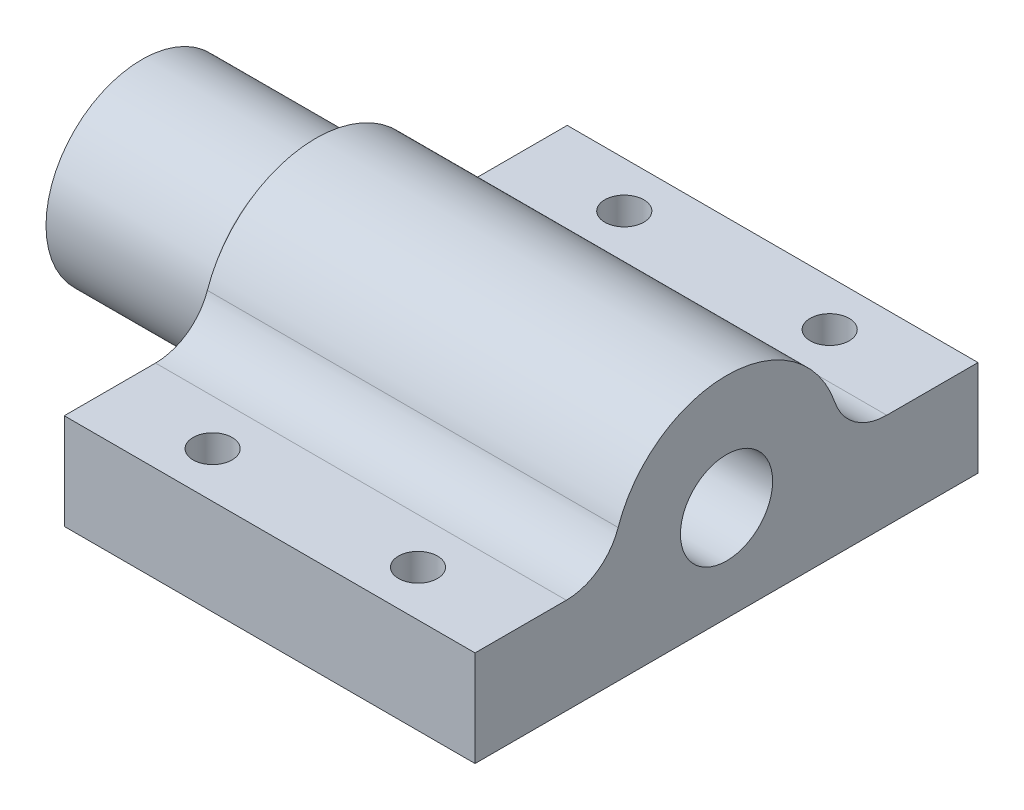
SolidWorks part; units mm, degrees
ref_plane "Front Plane" through (0, 0, 0) normal (0, 0, 1) x (1, 0, 0)
ref_plane "Top Plane" through (0, 0, 0) normal (0, 1, 0) x (1, 0, 0)
ref_plane "Right Plane" through (0, 0, 0) normal (1, 0, 0) x (0, 0, -1)
sketch "Sketch1" plane through (0, 0, 0) normal (1, 0, 0) x (0, 0, -1)
  line L0 (-11.7007, 0) -> (-18.3655, 0)
  line L1 (-18.3655, 0) -> (-18.3655, -7)
  line L2 (-18.3655, -7) -> (18.3655, -7)
  line L3 (0, 0) -> (0, -30.6301) construction
  line L4 (18.3655, 0) -> (18.3655, -7)
  line L5 (11.7007, 0) -> (18.3655, 0)
  circle A0 centre (0, 0) radius 3.3655
  arc A1 (7.9157, 2.7061) -> (-7.9157, 2.7061) centre (0, 0) ccw
  arc A2 (11.7007, 0) -> (7.9157, 2.7061) centre (11.7007, 4) cw
  arc A3 (-11.7007, 0) -> (-7.9157, 2.7061) centre (-11.7007, 4) ccw
  point P10 (0, -7)
  point P13 (8.3655, 0)
  point P16 (-8.3655, 0)
  dimension "D1" = 5
  dimension "D2" = 6.731
  dimension "D5" = 4
  dimension "D3" = 7
  dimension "D4" = 10
extrude "Boss-Extrude1" add sketch "Sketch1" along normal blind 30
ref_plane "Plane1" through (0, 0, 0) normal (0, 0, 1) x (1, 0, 0)
sketch "Sketch2" plane through (0, 0, 0) normal (0, 1, 0) x (1, 0, 0)
  line L0 (0, -15.0331) -> (7.5, -15.0331) construction
  line L1 (0, -11.7007) -> (0, -18.3655) construction
  line L2 (7.5, -15.0331) -> (15, -15.0331) construction
  line L3 (15, -15.0331) -> (22.5, -15.0331) construction
  line L4 (22.5, -15.0331) -> (30, -15.0331) construction
  line L5 (30, -11.7007) -> (30, -18.3655) construction
  line L6 (0, 0) -> (33.5291, 0) construction
  circle A0 centre (7.5, -15.0331) radius 1.425
  circle A1 centre (22.5, -15.0331) radius 1.425
  circle A2 centre (7.5, 15.0331) radius 1.425
  circle A3 centre (22.5, 15.0331) radius 1.425
  dimension "D1" = 2.85
extrude "Cut-Extrude1" cut sketch "Sketch2" against normal up to next
sketch "Sketch3" plane through (0, 0, 0) normal (-1, 0, 0) x (0, 0, 1)
  circle A0 centre (0, 0) radius 7
  circle A1 centre (0, 0) radius 3.3655
extrude "Boss-Extrude2" add sketch "Sketch3" along normal blind 12.7
fillet "Fillet1" radius 1 1 edges at (0, 0, 7)
